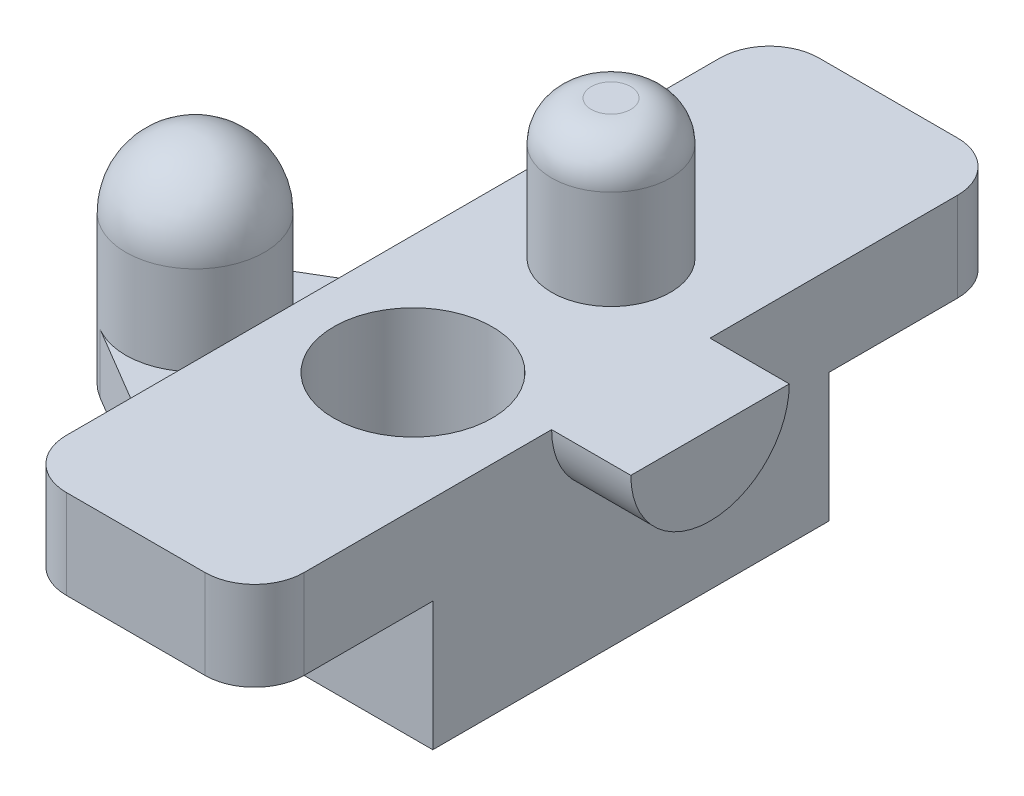
SolidWorks part; units mm, degrees
other "Markup1"
sketch "Sketch7" plane through (12, 7.5, 6.5) normal (0.0383, 0.9456, 0.3232) x (0.9932, -0.0006, -0.1161)
ref_plane "Front Plane" through (0, 0, 0) normal (0, 0, 1) x (1, 0, 0)
ref_plane "Top Plane" through (0, 0, 0) normal (0, 1, 0) x (1, 0, 0)
ref_plane "Right Plane" through (0, 0, 0) normal (1, 0, 0) x (0, 0, -1)
sketch "Sketch1" plane through (0, 0, 0) normal (0, 1, 0) x (1, 0, 0)
  line L0 (5, 5) -> (11, 5)
  line L1 (11, 5) -> (11, -5)
  line L2 (11, -5) -> (5, -5)
  line L3 (5, -5) -> (-0.8927, -1.5052)
  line L4 (5, 5) -> (-0.8927, 1.5052)
  arc A0 (-0.8927, 1.5052) -> (-0.8927, -1.5052) centre (0, 0) ccw
  point P11 (11, 0)
  dimension "D1" = 10
  dimension "D4" = 5
  dimension "D5" = 1.75
  dimension "D2" = 6
  dimension "D3" = 6
extrude "Boss-Extrude1" add sketch "Sketch1" against normal blind 1.5 contours L1 L2 L3 A0 L4 L0
sketch "Sketch2" plane through (0, 0, 0) normal (0, 1, 0) x (1, 0, 0)
  line L1 (5, 5) -> (11, 5)
  line L2 (5, 5) -> (5, -5)
  line L3 (5, -5) -> (11, -5)
  line L4 (11, 5) -> (11, -5)
  circle A0 centre (0, 0) radius 1.75
  dimension "D1" = 3.5
extrude "Boss-Extrude2" add sketch "Sketch2" along normal blind 4
sketch "Sketch3" plane through (0, 4, 0) normal (0, 1, 0) x (1, 0, 0)
  line L0 (5, 5) -> (11, 5)
  line L4 (-55, 0) -> (55, 0) construction
  line L6 (5, -5) -> (11, -5)
  line L7 (5, 5) -> (5, 8.25)
  line L8 (6.25, 9.5) -> (9.75, 9.5)
  line L9 (11, 8.25) -> (11, 5)
  line L10 (11, -8.25) -> (11, -5)
  line L11 (6.25, -9.5) -> (9.75, -9.5)
  line L12 (5, -5) -> (5, -8.25)
  arc A4 (5, 8.25) -> (6.25, 9.5) centre (6.25, 8.25) cw
  arc A5 (11, 8.25) -> (9.75, 9.5) centre (9.75, 8.25) ccw
  arc A6 (11, -8.25) -> (9.75, -9.5) centre (9.75, -8.25) cw
  arc A7 (5, -8.25) -> (6.25, -9.5) centre (6.25, -8.25) ccw
  dimension "D2" = 1.25
  dimension "D1" = 4.5
extrude "Boss-Extrude3" add sketch "Sketch3" against normal blind 2.25
fillet "Fillet1" radius 1.75 1 edges at (0, 4, 1.75)
sketch "Sketch4" plane through (0, 4, 0) normal (0, 1, 0) x (1, 0, 0)
  line L0 (5, 8.25) -> (5, -8.25) construction
  circle A0 centre (8, 2.5) radius 1.5
  dimension "D1" = 3
  dimension "D2" = 3
  dimension "D3" = 2.5
extrude "Boss-Extrude4" add sketch "Sketch4" along normal blind 3.5
fillet "Fillet2" radius 1 1 edges at (8, 7.5, -1)
sketch "Sketch5" plane through (0, 4, 0) normal (0, 1, 0) x (1, 0, 0)
  line L0 (5, 8.25) -> (5, -8.25) construction
  circle A0 centre (8, -2.5) radius 2
  dimension "D1" = 4
  dimension "D2" = 2.5
  dimension "D3" = 3
extrude "Cut-Extrude1" cut sketch "Sketch5" against normal blind 3.75
sketch "Sketch6" plane through (11, 0, 0) normal (1, 0, 0) x (0, 0, -1)
  line L0 (-8.25, 4) -> (8.25, 4) construction
  line L1 (-2, 4) -> (2, 4)
  arc A0 (-2, 4) -> (2, 4) centre (0, 4) ccw
  dimension "D1" = 4
extrude "Boss-Extrude5" add sketch "Sketch6" along normal blind 2
